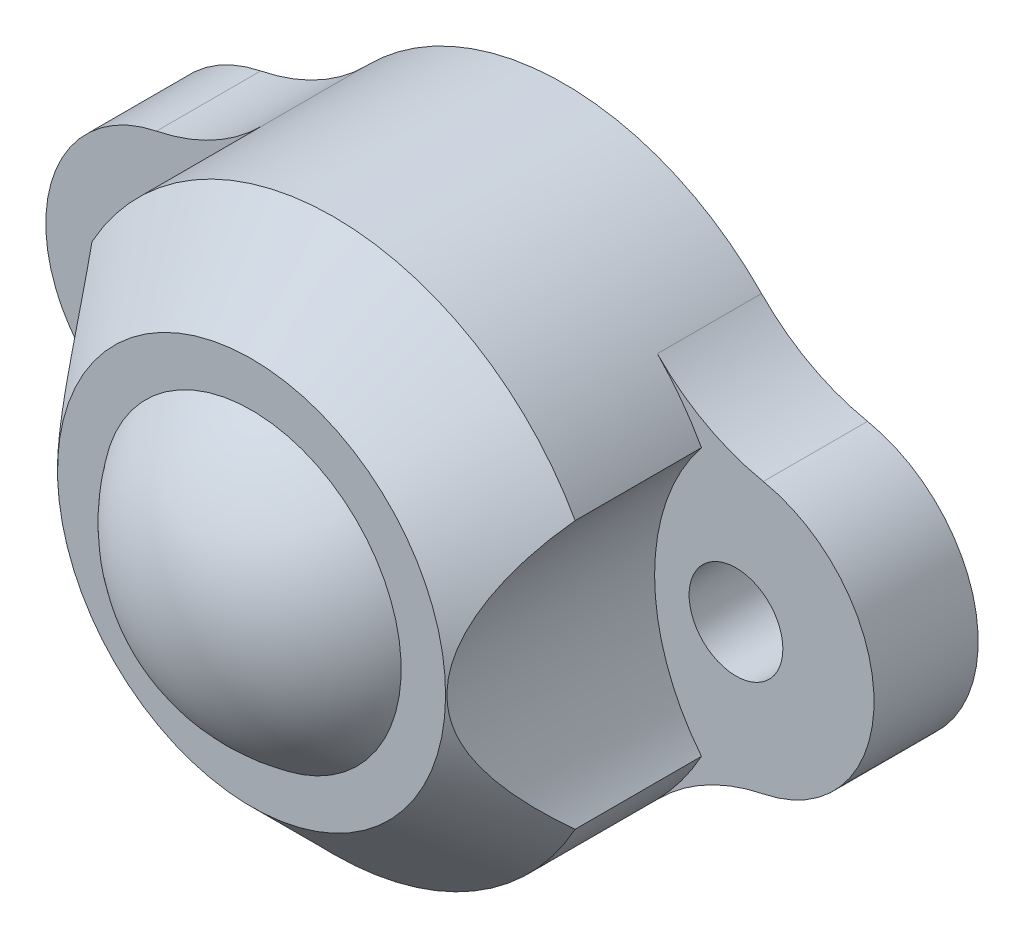
SolidWorks part; units mm, degrees
ref_plane "Front Plane" through (0, 0, 0) normal (0, 0, 1) x (1, 0, 0)
ref_plane "Top Plane" through (0, 0, 0) normal (0, 1, 0) x (1, 0, 0)
ref_plane "Right Plane" through (0, 0, 0) normal (1, 0, 0) x (0, 0, -1)
sketch "Sketch1" plane through (0, 0, 0) normal (0, 0, 1) x (1, 0, 0)
  line L0 (-6.731, 0) -> (6.731, 0) construction
  arc A0 (-5.8896, -3.2586) -> (5.8896, -3.2586) centre (0, 0) ccw
  arc A1 (-5.8896, 3.2586) -> (-5.8896, -3.2586) centre (-6.731, 0) ccw
  arc A2 (5.8896, -3.2586) -> (5.8896, 3.2586) centre (6.731, 0) ccw
  arc A3 (5.8896, 3.2586) -> (-5.8896, 3.2586) centre (0, 0) ccw
  circle A4 centre (-6.731, 0) radius 1.143
  circle A5 centre (6.731, 0) radius 1.143
  dimension "D1" = 13.462
  dimension "D2" = 2.286
  dimension "D3" = 3.3655
extrude "Boss-Extrude2" add sketch "Sketch1" along normal blind 2.54
sketch "Sketch3" plane through (0, 0, 2.54) normal (0, 0, 1) x (1, 0, 0)
  line L0 (0, -6.731) -> (0, 6.731) construction
  arc A0 (5.8896, 3.2586) -> (-5.8896, 3.2586) centre (0, 0) ccw construction
  arc A1 (-5.8896, -3.2586) -> (5.8896, -3.2586) centre (0, 0) ccw construction
  arc A2 (5.8896, 3.2586) -> (-5.8896, 3.2586) centre (0, 0) ccw
  arc A3 (-5.8896, -3.2586) -> (5.8896, -3.2586) centre (0, 0) ccw
  arc A4 (-5.8896, -3.2586) -> (-5.8896, 3.2586) centre (-9.9638, 0) ccw
  arc A5 (5.8896, -3.2586) -> (5.8896, 3.2586) centre (9.9638, 0) cw
  dimension "D1" = 5.2171
extrude "Boss-Extrude3" add sketch "Sketch3" along normal blind 5.08
ref_plane "Plane1" through (0, 0, 5.08) normal (0, 0, 1) x (1, 0, 0)
ref_axis "Axis1" through (-11.1062, 0, 5.08) along (1, 0, 0)
sketch "Sketch5" plane through (0, 0, 5.08) normal (0, 0, 1) x (1, 0, 0)
  line L0 (-13.8253, 0) -> (13.8253, 0) construction
  line L1 (-4.445, 0) -> (4.445, 0)
  arc A0 (-4.445, 0) -> (4.445, 0) centre (0, 0) cw
  dimension "D1" = 8.89
revolve "Revolve1" add sketch "Sketch5" angle 360 about L0
fillet "Fillet1" radius 5 4 edges at (-5.8896, 3.2586, 1.27) (5.8896, 3.2586, 1.27) (5.8896, -3.2586, 1.27) (-5.8896, -3.2586, 1.27)
chamfer "Chamfer1" distance 2 angle 45 1 edges at (0, -6.731, 7.62)
